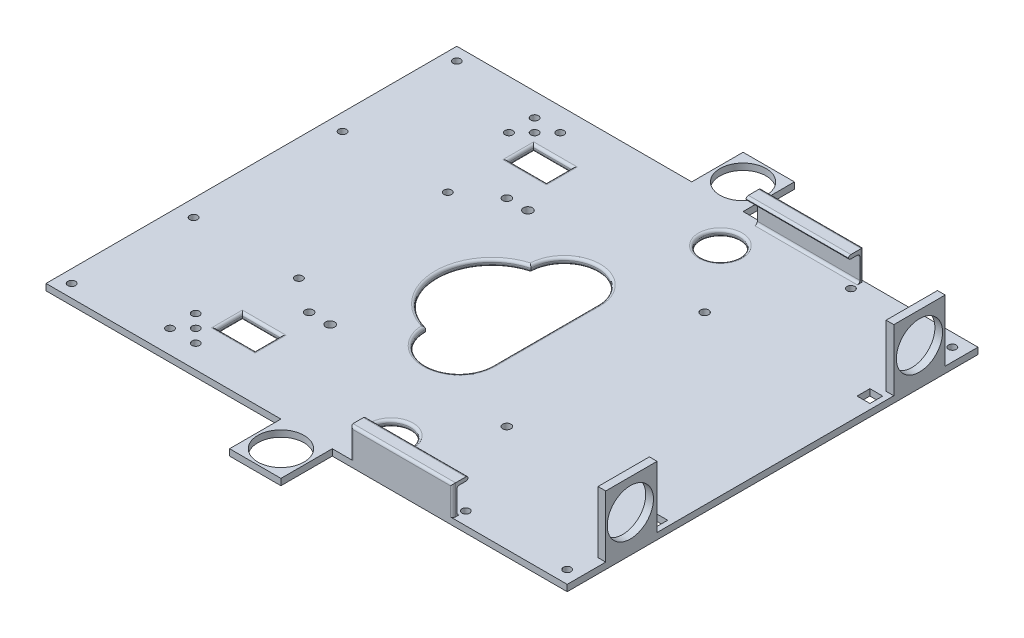
SolidWorks part; units mm, degrees
ref_plane "前视基准面" through (0, 0, 0) normal (0, 0, 1) x (1, 0, 0)
ref_plane "上视基准面" through (0, 0, 0) normal (0, 1, 0) x (1, 0, 0)
ref_plane "右视基准面" through (0, 0, 0) normal (1, 0, 0) x (0, 0, -1)
other "Configuration Table"
sketch "草图1" plane through (0, 0, 0) normal (0, 0, 1) x (1, 0, 0)
  line L0 (0, 0) -> (203, 0)
  line L1 (0, 0) -> (0, 2.5)
  line L2 (0, 2.5) -> (79, 2.5)
  line L3 (79, 2.5) -> (79, 32.5)
  line L4 (79, 32.5) -> (81.5, 32.5)
  line L5 (81.5, 32.5) -> (81.5, 2.5)
  line L6 (81.5, 2.5) -> (124, 2.5)
  line L7 (126.5, 2.5) -> (126.5, 32.5)
  line L8 (126.5, 32.5) -> (124, 32.5)
  line L9 (124, 32.5) -> (124, 2.5)
  line L11 (203, 2.5) -> (203, 0)
  line L12 (126.5, 2.5) -> (203, 2.5)
  dimension "D1" = 203
  dimension "D2" = 79
  dimension "D3" = 79
  dimension "D4" = 42.5
  dimension "D5" = 2.5
  dimension "D6" = 2.5
  dimension "D7" = 2.5
  dimension "D8" = 30
  dimension "D9" = 30
  dimension "D10" = 2.5
extrude "凸台-拉伸2" add sketch "草图1" along normal blind 160
fillet "圆角1" radius 1 1 edges at (81.5, 2.5, 80)
fillet "圆角2" radius 1 1 edges at (124, 2.5, 80)
fillet "圆角3" radius 1 2 edges at (79, 2.5, 80) (126.5, 2.5, 80)
sketch "草图2" plane through (0, 2.5, 0) normal (0, 1, 0) x (1, 0, 0)
  line L0 (78, 0) -> (0, 0) construction
  line L1 (0, -160) -> (0, 0) construction
  line L2 (78, -160) -> (0, -160) construction
  line L3 (203, -160) -> (203, 0) construction
  line L4 (203, 0) -> (127.5, 0) construction
  line L6 (203, -160) -> (127.5, -160) construction
  circle A0 centre (5, -5) radius 1.5
  circle A1 centre (5, -155) radius 1.5
  circle A2 centre (198, -5) radius 1.5
  circle A3 centre (198, -155) radius 1.5
  dimension "D9" = 3
  dimension "D10" = 3
  dimension "D11" = 3
  dimension "D12" = 3
  dimension "D1" = 5
  dimension "D2" = 5
  dimension "D3" = 5
  dimension "D4" = 5
  dimension "D5" = 5
  dimension "D6" = 5
  dimension "D7" = 5
  dimension "D8" = 5
extrude "切除-拉伸1" cut sketch "草图2" against normal blind 160
sketch "草图3" plane through (0, 2.5, 0) normal (0, 1, 0) x (1, 0, 0)
  line L1 (203, -160) -> (203, 0) construction
  line L4 (203, 0) -> (127.5, 0) construction
  circle A2 centre (158.5, -5) radius 1.5
  circle A3 centre (158.5, -155) radius 1.5
  dimension "D3" = 3
  dimension "D4" = 3
  dimension "D7" = 44.5
  dimension "D8" = 44.5
  dimension "D9" = 5
extrude "切除-拉伸2" cut sketch "草图3" against normal blind 160
sketch "草图4" plane through (0, 2.5, 0) normal (0, 1, 0) x (1, 0, 0)
  line L0 (23.0924, -35.8152) -> (60.3028, -35.8152) construction
  line L3 (23.0924, -32.1909) -> (60.3028, -32.1909)
  line L4 (23.0924, -39.4396) -> (60.3028, -39.4396)
  line L5 (23.0924, -69.4396) -> (60.3028, -69.4396)
  line L6 (23.0924, -62.1909) -> (60.3028, -62.1909)
  line L7 (23.0924, -65.8152) -> (60.3028, -65.8152) construction
  line L8 (23.0924, -99.4396) -> (60.3028, -99.4396)
  line L9 (23.0924, -92.1909) -> (60.3028, -92.1909)
  line L10 (23.0924, -95.8152) -> (60.3028, -95.8152) construction
  line L11 (23.0924, -129.4396) -> (60.3028, -129.4396)
  line L12 (23.0924, -122.1909) -> (60.3028, -122.1909)
  line L13 (23.0924, -125.8152) -> (60.3028, -125.8152) construction
  arc A2 (23.0924, -32.1909) -> (23.0924, -39.4396) centre (23.0924, -35.8152) ccw
  arc A3 (60.3028, -39.4396) -> (60.3028, -32.1909) centre (60.3028, -35.8152) ccw
  arc A4 (23.0924, -62.1909) -> (23.0924, -69.4396) centre (23.0924, -65.8152) ccw
  arc A5 (60.3028, -69.4396) -> (60.3028, -62.1909) centre (60.3028, -65.8152) ccw
  arc A6 (23.0924, -92.1909) -> (23.0924, -99.4396) centre (23.0924, -95.8152) ccw
  arc A7 (60.3028, -99.4396) -> (60.3028, -92.1909) centre (60.3028, -95.8152) ccw
  arc A8 (23.0924, -122.1909) -> (23.0924, -129.4396) centre (23.0924, -125.8152) ccw
  arc A9 (60.3028, -129.4396) -> (60.3028, -122.1909) centre (60.3028, -125.8152) ccw
  point P2 (41.6976, -35.8152)
  point P11 (41.6976, -65.8152)
  point P18 (41.6976, -95.8152)
  point P25 (41.6976, -125.8152)
  dimension "D1" = 4
sketch "草图5" plane through (0, 2.5, 0) normal (0, 1, 0) x (1, 0, 0)
  line L0 (143.7888, -31.7728) -> (177.4701, -31.7728) construction
  line L1 (143.7888, -28.5294) -> (177.4701, -28.5294)
  line L2 (143.7888, -35.0162) -> (177.4701, -35.0162)
  line L3 (143.7888, -61.7728) -> (177.4701, -61.7728) construction
  line L4 (143.7888, -58.5294) -> (177.4701, -58.5294)
  line L5 (143.7888, -65.0162) -> (177.4701, -65.0162)
  line L6 (143.7888, -91.7728) -> (177.4701, -91.7728) construction
  line L7 (143.7888, -88.5294) -> (177.4701, -88.5294)
  line L8 (143.7888, -95.0162) -> (177.4701, -95.0162)
  line L9 (143.7888, -121.7728) -> (177.4701, -121.7728) construction
  line L10 (143.7888, -118.5294) -> (177.4701, -118.5294)
  line L11 (143.7888, -125.0162) -> (177.4701, -125.0162)
  arc A0 (143.7888, -28.5294) -> (143.7888, -35.0162) centre (143.7888, -31.7728) ccw
  arc A1 (177.4701, -35.0162) -> (177.4701, -28.5294) centre (177.4701, -31.7728) ccw
  arc A2 (143.7888, -58.5294) -> (143.7888, -65.0162) centre (143.7888, -61.7728) ccw
  arc A3 (177.4701, -65.0162) -> (177.4701, -58.5294) centre (177.4701, -61.7728) ccw
  arc A4 (143.7888, -88.5294) -> (143.7888, -95.0162) centre (143.7888, -91.7728) ccw
  arc A5 (177.4701, -95.0162) -> (177.4701, -88.5294) centre (177.4701, -91.7728) ccw
  arc A6 (143.7888, -118.5294) -> (143.7888, -125.0162) centre (143.7888, -121.7728) ccw
  arc A7 (177.4701, -125.0162) -> (177.4701, -118.5294) centre (177.4701, -121.7728) ccw
  point P2 (160.6294, -31.7728)
  point P11 (160.6294, -61.7728)
  point P18 (160.6294, -91.7728)
  point P25 (160.6294, -121.7728)
  dimension "D1" = 4
sketch "草图6" plane through (126.5, 0, 0) normal (1, 0, 0) x (0, 0, -1)
  line L0 (-18.1958, 24.2889) -> (-18.1958, 13.2086) construction
  line L1 (-15.5576, 24.2889) -> (-15.5576, 13.2086)
  line L2 (-20.834, 24.2889) -> (-20.834, 13.2086)
  line L3 (-38.1958, 24.2889) -> (-38.1958, 13.2086) construction
  line L4 (-35.5576, 24.2889) -> (-35.5576, 13.2086)
  line L5 (-40.834, 24.2889) -> (-40.834, 13.2086)
  line L6 (-58.1958, 24.2889) -> (-58.1958, 13.2086) construction
  line L7 (-55.5576, 24.2889) -> (-55.5576, 13.2086)
  line L8 (-60.834, 24.2889) -> (-60.834, 13.2086)
  line L9 (-78.1958, 24.2889) -> (-78.1958, 13.2086) construction
  line L10 (-75.5576, 24.2889) -> (-75.5576, 13.2086)
  line L11 (-80.834, 24.2889) -> (-80.834, 13.2086)
  line L12 (-98.1958, 24.2889) -> (-98.1958, 13.2086) construction
  line L13 (-95.5576, 24.2889) -> (-95.5576, 13.2086)
  line L14 (-100.834, 24.2889) -> (-100.834, 13.2086)
  line L15 (-118.1958, 24.2889) -> (-118.1958, 13.2086) construction
  line L16 (-115.5576, 24.2889) -> (-115.5576, 13.2086)
  line L17 (-120.834, 24.2889) -> (-120.834, 13.2086)
  line L18 (-138.1958, 24.2889) -> (-138.1958, 13.2086) construction
  line L19 (-135.5576, 24.2889) -> (-135.5576, 13.2086)
  line L20 (-140.834, 24.2889) -> (-140.834, 13.2086)
  arc A0 (-15.5576, 24.2889) -> (-20.834, 24.2889) centre (-18.1958, 24.2889) ccw
  arc A1 (-20.834, 13.2086) -> (-15.5576, 13.2086) centre (-18.1958, 13.2086) ccw
  arc A2 (-35.5576, 24.2889) -> (-40.834, 24.2889) centre (-38.1958, 24.2889) ccw
  arc A3 (-40.834, 13.2086) -> (-35.5576, 13.2086) centre (-38.1958, 13.2086) ccw
  arc A4 (-55.5576, 24.2889) -> (-60.834, 24.2889) centre (-58.1958, 24.2889) ccw
  arc A5 (-60.834, 13.2086) -> (-55.5576, 13.2086) centre (-58.1958, 13.2086) ccw
  arc A6 (-75.5576, 24.2889) -> (-80.834, 24.2889) centre (-78.1958, 24.2889) ccw
  arc A7 (-80.834, 13.2086) -> (-75.5576, 13.2086) centre (-78.1958, 13.2086) ccw
  arc A8 (-95.5576, 24.2889) -> (-100.834, 24.2889) centre (-98.1958, 24.2889) ccw
  arc A9 (-100.834, 13.2086) -> (-95.5576, 13.2086) centre (-98.1958, 13.2086) ccw
  arc A10 (-115.5576, 24.2889) -> (-120.834, 24.2889) centre (-118.1958, 24.2889) ccw
  arc A11 (-120.834, 13.2086) -> (-115.5576, 13.2086) centre (-118.1958, 13.2086) ccw
  arc A12 (-135.5576, 24.2889) -> (-140.834, 24.2889) centre (-138.1958, 24.2889) ccw
  arc A13 (-140.834, 13.2086) -> (-135.5576, 13.2086) centre (-138.1958, 13.2086) ccw
  point P2 (-18.1958, 18.7488)
  point P11 (-38.1958, 18.7488)
  point P18 (-58.1958, 18.7488)
  point P25 (-78.1958, 18.7488)
  point P32 (-98.1958, 18.7488)
  point P39 (-118.1958, 18.7488)
  point P46 (-138.1958, 18.7488)
  dimension "D1" = 7
extrude "切除-拉伸5" cut sketch "草图6" against normal blind 160
sketch "草图7" plane through (79, 0, 0) normal (-1, 0, 0) x (0, 0, 1)
  line L4 (0, 32.5) -> (0, 3.5)
  line L5 (0, 3.5) -> (160, 3.5)
  line L6 (160, 3.5) -> (160, 32.5)
  line L7 (160, 32.5) -> (0, 32.5)
  line L8 (0, 32.5) -> (0, 3.5)
  line L9 (0, 3.5) -> (160, 3.5)
  line L10 (160, 3.5) -> (160, 32.5)
  line L11 (160, 32.5) -> (0, 32.5)
  dimension "D1" = 0
extrude "切除-拉伸6" cut sketch "草图7" against normal through all
sketch "草图8" plane through (0, 3.5, 0) normal (0, 1, 0) x (1, 0, 0)
  line L4 (124, -160) -> (126.5, -160)
  line L5 (126.5, -160) -> (126.5, 0)
  line L6 (126.5, 0) -> (124, 0)
  line L7 (124, 0) -> (124, -160)
  line L8 (124, -160) -> (126.5, -160)
  line L9 (126.5, -160) -> (126.5, 0)
  line L10 (126.5, 0) -> (124, 0)
  line L11 (124, 0) -> (124, -160)
  dimension "D1" = 0
extrude "切除-拉伸7" cut sketch "草图8" against normal up to surface (1 mm away) up to face at (102.75, 2.5, 80)
sketch "草图9" plane through (124, 0, 0) normal (1, 0, 0) x (0, 0, -1)
  line L4 (0, 2.5) -> (0, 3.5)
  line L5 (0, 3.5) -> (-160, 3.5)
  line L6 (-160, 3.5) -> (-160, 2.5)
  line L7 (-160, 2.5) -> (0, 2.5)
  line L8 (0, 2.5) -> (0, 3.5)
  line L9 (0, 3.5) -> (-160, 3.5)
  line L10 (-160, 3.5) -> (-160, 2.5)
  line L11 (-160, 2.5) -> (0, 2.5)
  dimension "D1" = 0
extrude "切除-拉伸8" cut sketch "草图9" against normal mid plane 100
sketch "草图10" plane through (0, 2.5, 0) normal (0, 1, 0) x (1, 0, 0)
  line L0 (101.5, 0) -> (101.5, -160) construction
  line L1 (203, 0) -> (0, 0) construction
  line L2 (203, -160) -> (0, -160) construction
  line L3 (0, -80) -> (203, -80) construction
  line L4 (0, -160) -> (0, 0) construction
  line L5 (203, -160) -> (203, 0) construction
sketch "草图12" plane through (0, 0, 160) normal (0, 0, 1) x (1, 0, 0)
  line L0 (101.5, 2.5) -> (111.5, 2.5)
  line L1 (0, 2.5) -> (203, 2.5) construction
  line L2 (101.5, 2.5) -> (91.5, 2.5)
  line L3 (101.5, 2.5) -> (101.5, 0) construction
  line L4 (0, 0) -> (203, 0) construction
  line L5 (101.5, 0) -> (111.5, 0)
  line L6 (101.5, 0) -> (91.5, 0)
  line L7 (91.5, 2.5) -> (91.5, 0)
  line L8 (111.5, 0) -> (111.5, 2.5)
  dimension "D1" = 10
  dimension "D2" = 10
  dimension "D3" = 10
  dimension "D4" = 10
extrude "凸台-拉伸3" add sketch "草图12" along normal blind 20 contours L8 L0 L2 L7 L6 L5
sketch "草图13" plane through (0, 0, 180) normal (0, 0, 1) x (1, 0, 0)
  line L4 (91.5, 0) -> (111.5, 0)
  line L5 (111.5, 0) -> (111.5, 2.5)
  line L6 (111.5, 2.5) -> (91.5, 2.5)
  line L7 (91.5, 2.5) -> (91.5, 0)
  line L8 (91.5, 0) -> (111.5, 0)
  line L9 (111.5, 0) -> (111.5, 2.5)
  line L10 (111.5, 2.5) -> (91.5, 2.5)
  line L11 (91.5, 2.5) -> (91.5, 0)
  dimension "D1" = 0
extrude "凸台-拉伸4" add sketch "草图13" against normal offset from surface (200 mm away) 20 contours L8 L9 L10 L11 up to face at (101.5, 1.25, 0) offset beyond the face yes
sketch "草图14" plane through (0, 2.5, 0) normal (0, 1, 0) x (1, 0, 0)
  line L0 (91.5, 20) -> (111.5, 0) construction
  line L1 (111.5, 20) -> (91.5, 0) construction
  line L2 (91.5, -160) -> (111.5, -180) construction
  line L3 (111.5, -160) -> (91.5, -180) construction
  circle A0 centre (101.5, -170) radius 9
  circle A1 centre (101.5, 10) radius 9
  dimension "D1" = 18
  dimension "D2" = 18
extrude "切除-拉伸9" cut sketch "草图14" against normal blind 20
sketch "草图15" plane through (0, 2.5, 0) normal (0, 1, 0) x (1, 0, 0)
  line L0 (0, -80) -> (203, -80)
  line L1 (203, -160) -> (203, 0) construction
  line L2 (61, -48.5123) -> (138, -48.5123) construction
  line L3 (101.5, -39.7034) -> (101.5, -61.13) construction
  line L4 (101.5, 0) -> (101.5, -160) construction
  line L5 (101.5, -48.5123) -> (138, -48.5123) construction
  circle A0 centre (138, -41.5) radius 1.6
  circle A1 centre (138, -118.5) radius 1.6
  circle A2 centre (61, -41.5) radius 1.6
  circle A3 centre (61, -118.5) radius 1.6
  circle A4 centre (129.8, -41.5) radius 1.75
  circle A5 centre (129.8, -118.5) radius 1.75
  dimension "D3" = 3.2
  dimension "D5" = 3.2
  dimension "D7" = 77
  dimension "D8" = 3.5
  dimension "D1" = 77
  dimension "D2" = 65
  dimension "D4" = 77
  dimension "D6" = 8.2
  dimension "D9" = 36.5
extrude "切除-拉伸10" cut sketch "草图15" against normal through all contours A2 | A0 | A3 | A1
sketch "草图16" plane through (0, 2.5, 0) normal (0, 1, 0) x (1, 0, 0)
  line L0 (114.4825, -100.4876) -> (114.4825, -59.5124)
  line L1 (0, -80) -> (203, -80) construction
  line L2 (0, -160) -> (0, 0) construction
  line L3 (88.3681, -59.5124) -> (114.4825, -59.5124) construction
  line L8 (101.5, -100.4876) -> (101.5, -59.5124) construction
  line L10 (101.5, -46.5299) -> (82.3521, -46.5299) construction
  line L11 (101.5, -113.4701) -> (79.2618, -113.4701) construction
  circle A1 centre (118.569, -15.8966) radius 7.5
  circle A3 centre (118.569, -144.1034) radius 7.5
  arc A8 (88.3681, -59.5124) -> (88.3681, -100.4876) centre (93.7203, -80) ccw
  arc A11 (88.3681, -59.5124) -> (114.4825, -59.5124) centre (101.4253, -59.5873) cw
  arc A12 (88.3681, -100.4876) -> (114.4825, -100.4876) centre (101.4253, -100.4876) ccw
  dimension "D2" = 15
extrude "切除-拉伸12" cut sketch "草图16" against normal through all
sketch "草图17" plane through (0, 2.5, 0) normal (0, 1, 0) x (1, 0, 0)
  line L0 (0, -80) -> (203, -80)
  line L1 (0, -160) -> (0, 0) construction
  circle A0 centre (6.5, -51) radius 1.5
  circle A3 centre (6.5, -109) radius 1.5
  circle A4 centre (47.5, -51) radius 1.5
  circle A6 centre (47.5, -109) radius 1.5
  dimension "D3" = 3
  dimension "D4" = 41
  dimension "D5" = 3
  dimension "D1" = 6.5
  dimension "D2" = 29
sketch "草图18" plane through (0, 2.5, 0) normal (0, 1, 0) x (1, 0, 0)
extrude "切除-拉伸14" cut sketch "草图17" against normal blind 10 contours A0 | A3 | A6 | A4
sketch "草图20" plane through (0, 2.5, 0) normal (0, 1, 0) x (1, 0, 0)
  line L0 (91.5, 0) -> (0, 0) construction
  line L1 (57.115, 0) -> (77.115, 0)
  line L2 (57.115, 0) -> (57.115, -4)
  line L3 (57.115, -4) -> (77.115, -4)
  line L4 (77.115, 0) -> (77.115, -4)
  line L5 (0, -80) -> (203, -80)
  line L6 (57.115, -156) -> (77.115, -156)
  line L7 (77.115, -160) -> (77.115, -156)
  line L8 (57.115, -160) -> (77.115, -160)
  line L9 (57.115, -160) -> (57.115, -156)
  dimension "D1" = 20
  dimension "D2" = 4
sketch "草图23" plane through (0, 2.5, 0) normal (0, 1, 0) x (1, 0, 0)
  line L1 (48.2117, -131.7341) -> (63.2117, -131.7341)
  line L2 (48.2117, -131.7341) -> (48.2117, -141.7341)
  line L3 (48.2117, -141.7341) -> (63.2117, -141.7341)
  line L4 (63.2117, -131.7341) -> (63.2117, -141.7341)
  dimension "D1" = 15
  dimension "D2" = 10
extrude "切除-拉伸16" cut sketch "草图23" against normal blind 10
sketch "草图24" plane through (0, 2.5, 0) normal (0, 1, 0) x (1, 0, 0)
  line L0 (0, -80) -> (203, -80)
  line L1 (200, -12.7863) -> (203, -12.7863)
  line L2 (203, -160) -> (203, 0) construction
  line L3 (203, -12.7863) -> (203, -32.7863)
  line L4 (203, -32.7863) -> (200, -32.7863)
  line L5 (200, -32.7863) -> (200, -12.7863)
  line M42 (203, -160) -> (203, 0)
  dimension "D1" = 3
  dimension "D2" = 20
extrude "凸台-拉伸8" add sketch "草图24" along normal blind 24 contours L5 L4 L1 M42 region at (201.5, 2.5, 22.7863)
sketch "草图25" plane through (203, 0, 0) normal (1, 0, 0) x (0, 0, -1)
  line L0 (-32.7863, 26.5) -> (-12.7863, 2.5) construction
  line L1 (0, 2.5) -> (-160, 2.5) construction
  line L2 (-12.7863, 26.5) -> (-12.7863, 2.5) construction
  line L3 (-12.7863, 26.5) -> (-32.7863, 2.5) construction
  circle A0 centre (-22.7863, 14.5) radius 9
  dimension "D1" = 18
extrude "切除-拉伸17" cut sketch "草图25" against normal blind 20
sketch "草图26" plane through (0, 2.5, 0) normal (0, 1, 0) x (1, 0, 0)
  line L0 (203, -145) -> (203, -125)
  line L1 (203, -160) -> (203, -32.7863) construction
  line L2 (203, -125) -> (200, -125)
  line L3 (200, -125) -> (200, -145)
  line L4 (200, -145) -> (203, -145)
  line L5 (203, -160) -> (111.5, -160) construction
  dimension "D1" = 3
  dimension "D2" = 15
  dimension "D3" = 20
extrude "凸台-拉伸9" add sketch "草图26" along normal blind 24
sketch "草图27" plane through (203, 0, 0) normal (1, 0, 0) x (0, 0, -1)
  line L0 (-145, 26.5) -> (-125.8152, 2.5) construction
  line L1 (-125, 26.5) -> (-145, 2.5) construction
  circle A0 centre (-135.4076, 14.5) radius 9
  dimension "D1" = 18
extrude "切除-拉伸18" cut sketch "草图27" against normal blind 20
sketch "草图32" plane through (0, 2.5, 0) normal (0, 1, 0) x (1, 0, 0)
  line L0 (62.6, -41.5) -> (69.2, -41.5)
  line L1 (69.2, -41.5) -> (69.2, -118.5)
  line L2 (69.2, -118.5) -> (59.4, -118.5)
  circle A0 centre (61, -41.5) radius 1.6 construction
  circle A1 centre (61, -118.5) radius 1.6 construction
  circle A2 centre (69.2, -41.5) radius 1.75
  circle A3 centre (69.2, -118.5) radius 1.75
  dimension "D3" = 3.5
  dimension "D4" = 3.5
  dimension "D1" = 6.6
  dimension "D2" = 9.8
extrude "切除-拉伸21" cut sketch "草图32" against normal blind 10 contours A3 | A2
sketch "草图33" plane through (0, 2.5, 0) normal (0, 1, 0) x (1, 0, 0)
  line L0 (57.115, -4) -> (77.115, -24) construction
  line L2 (57.115, -4) -> (57.115, -24)
  line L5 (57.115, -24) -> (77.115, -4) construction
  line L6 (67.115, -4) -> (67.115, -24) construction
  line L7 (57.115, -14) -> (77.115, -14) construction
  line L8 (0, -80) -> (203, -80) construction
  line L17 (48.2117, -131.7341) -> (48.2117, -141.7341) construction
  line L18 (48.2117, -136) -> (34.3084, -136)
  line L19 (33.5308, 0) -> (47.4341, 0)
  line L20 (34.3084, -136) -> (34.3084, -156)
  line L21 (34.3084, -156) -> (57.115, -156)
  line L22 (57.115, -156) -> (57.115, -141.7341)
  line L23 (48.2117, -141.7341) -> (63.2117, -141.7341) construction
  line L24 (48.2117, -136) -> (48.2117, -141.7341)
  line L25 (48.2117, -141.7341) -> (57.115, -141.7341)
  line L27 (48.2117, -24) -> (34.3084, -24)
  line L28 (34.3084, -24) -> (34.3084, -4)
  line L29 (34.3084, -4) -> (57.115, -4)
  line L30 (57.115, -4) -> (57.115, -18.2659)
  line L32 (48.2117, -24) -> (57.115, -24)
  circle A9 centre (39.3084, -141) radius 1.5
  circle A10 centre (39.3084, -151) radius 1.5
  circle A11 centre (49.3084, -151) radius 1.5
  circle A12 centre (44.3084, -146) radius 1.5
  circle A13 centre (39.3084, -9) radius 1.5
  circle A14 centre (49.3084, -9) radius 1.5
  circle A15 centre (44.3084, -14) radius 1.5
  circle A16 centre (39.3084, -19) radius 1.5
  dimension "D1" = 20
  dimension "D2" = 20
extrude "切除-拉伸22" cut sketch "草图33" against normal blind 10 contours A13 | A15 | A14 | A16 | A9 | A12 | A10 | A11
ref_plane "基准面1" through (0, 2.5, 160) normal (0, 0, -1) x (-1, 0, 0)
sketch "草图34" plane through (0, 2.5, 0) normal (0, 1, 0) x (1, 0, 0)
  line L0 (63.2117, -141.7341) -> (63.2117, -131.7341) construction
  line L1 (63.2117, -136.7341) -> (101.5, -136.7341) construction
  line L2 (101.5, 0) -> (101.5, -160) construction
  line L3 (63.2117, -131.7341) -> (101.5, -131.7341) construction
  line L4 (79.0313, -131.7341) -> (79.0313, -160) construction
  line L5 (91.5, -160) -> (0, -160) construction
sketch "草图36" plane through (0, 2.5, 0) normal (0, 1, 0) x (1, 0, 0)
  line L0 (203, -32.7863) -> (173.0843, -32.7863) construction
  line L1 (203, -80) -> (174.2547, -80) construction
  line L6 (200.9432, -35.0459) -> (195.9432, -35.0459)
  line L7 (200.9432, -35.0459) -> (200.9432, -40.0459)
  line L8 (200.9432, -40.0459) -> (195.9432, -40.0459)
  line L9 (195.9432, -35.0459) -> (195.9432, -40.0459)
  line L15 (200.9432, -123.8021) -> (195.9432, -123.8021)
  line L16 (200.9432, -123.8021) -> (200.9432, -118.8021)
  line L17 (200.9432, -118.8021) -> (195.9432, -118.8021)
  line L18 (195.9432, -123.8021) -> (195.9432, -118.8021)
extrude "切除-拉伸24" cut sketch "草图36" against normal through all
fillet "圆角5" radius 1 4 edges at (118.569, 0, 136.6034) (118.569, 2.5, 136.6034) (118.569, 0, 23.3966) (118.569, 2.5, 23.3966)
sketch "草图37" plane through (0, 2.5, 0) normal (0, 1, 0) x (1, 0, 0)
  line L0 (118.569, -15.8966) -> (118.569, 26.7933) construction
  line L1 (118.569, -144.1034) -> (118.569, -195.1785) construction
  line L2 (158.5, -5) -> (158.5, 17.229) construction
  line L3 (115.8495, 0) -> (163.8116, 0) construction
  line L4 (203, 0) -> (111.5, 0) construction
  line L5 (158.5, -155) -> (158.5, -133.8805) construction
  line L6 (118.569, 0) -> (158.5, 0)
  line L7 (118.569, 0) -> (118.569, -1.5)
  line L8 (118.569, -1.5) -> (158.5, -1.5)
  line L9 (158.5, 0) -> (158.5, -1.5)
  line L10 (158.5, -155) -> (158.5, -175.388) construction
  line L11 (115.3368, -160) -> (165.166, -160) construction
  line L12 (203, -160) -> (111.5, -160) construction
  line L14 (118.569, -160) -> (158.5, -160)
  line L15 (118.569, -160) -> (118.569, -158.5)
  line L16 (118.569, -158.5) -> (158.5, -158.5)
  line L17 (158.5, -160) -> (158.5, -158.5)
extrude "凸台-拉伸10" add sketch "草图37" along normal blind 10
sketch "草图38" plane through (0, 12.5, 0) normal (0, 1, 0) x (1, 0, 0)
  line L0 (158.5, 0) -> (158.5, -13.0357) construction
  line L2 (118.569, 0) -> (158.5, 0)
  line L3 (118.569, 0) -> (118.569, -6)
  line L4 (118.569, -6) -> (158.5, -6)
  line L5 (158.5, 0) -> (158.5, -6)
extrude "凸台-拉伸11" add sketch "草图38" along normal blind 1.5
fillet "圆角6" radius 1 7 edges at (138.5345, 2.5, 1.5) (138.5345, 12.5, 1.5) (138.5345, 14, 6) (138.5345, 12.5, 6) (118.569, 8.25, 0) (158.5, 8.25, 0) (138.5345, 14, 0)
ref_plane "基准面2" through (0, 0, 80) normal (0, 0, 1) x (1, 0, 0)
mirror "镜向2" about plane through (0, 0, 80) normal (0, 0, 1) of "凸台-拉伸11"
fillet "圆角7" radius 1 7 edges at (118.569, 8.25, 160) (158.5, 8.25, 160) (138.5345, 14, 160) (138.5345, 14, 154) (138.5345, 12.5, 154) (138.5345, 12.5, 158.5) (138.5345, 2.5, 158.5)
mirror "镜向3" about plane through (0, 0, 80) normal (0, 0, 1) of "切除-拉伸16"
fillet "圆角8" radius 1 16 edges at (48.2117, 2.5, 136.7341) (48.2117, 0, 136.7341) (55.7117, 0, 131.7341) (55.7117, 0, 141.7341) (55.7117, 2.5, 141.7341) (63.2117, 0, 136.7341) (55.7117, 2.5, 131.7341) (63.2117, 2.5, 136.7341) (48.2117, 2.5, 23.2659) (48.2117, 0, 23.2659) (55.7117, 0, 28.2659) (55.7117, 2.5, 28.2659) (63.2117, 0, 23.2659) (63.2117, 2.5, 23.2659) (55.7117, 0, 18.2659) (55.7117, 2.5, 18.2659)
fillet "圆角9" radius 1 8 edges at (101.4253, 2.5, 113.5448) (101.4253, 2.5, 46.5299) (114.4825, 0, 80) (114.4825, 2.5, 80) (101.4253, 0, 113.5448) (101.4253, 0, 46.5299) (72.5452, 0, 80) (72.5452, 2.5, 80)
